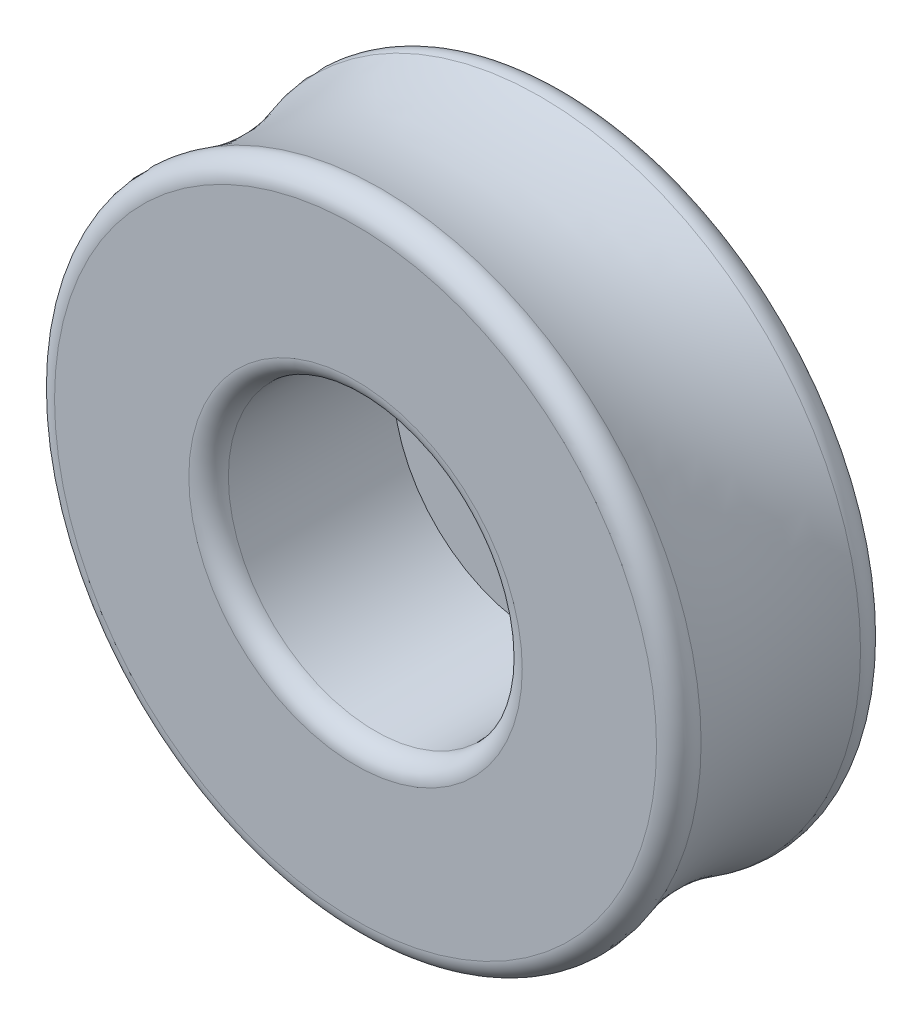
SolidWorks part; units mm, degrees
ref_plane "Front Plane" through (0, 0, 0) normal (0, 0, 1) x (1, 0, 0)
ref_plane "Top Plane" through (0, 0, 0) normal (0, 1, 0) x (1, 0, 0)
ref_plane "Right Plane" through (0, 0, 0) normal (1, 0, 0) x (0, 0, -1)
sketch "Sketch2" plane through (0, 0, 0) normal (0, 1, 0) x (1, 0, 0)
  line L1 (-12.5, -8) -> (12.5, -8)
  line L2 (-12.5, -8) -> (-12.5, 8)
  line L3 (-12.5, 8) -> (12.5, 8)
  line L4 (12.5, -8) -> (12.5, 8)
  line L5 (-12.5, -8) -> (12.5, 8) construction
  line L6 (-12.5, 8) -> (12.5, -8) construction
  line L7 (12.5, 8) -> (6.5, 8)
  line L8 (12.5, 8) -> (12.5, 15)
  line L9 (12.5, 15) -> (6.5, 15)
  line L10 (6.5, 8) -> (6.5, 15)
  line L11 (12.5, 15) -> (4.5, 15)
  line L12 (12.5, 15) -> (12.5, 17)
  line L13 (12.5, 17) -> (4.5, 17)
  line L14 (4.5, 15) -> (4.5, 17)
  arc A0 (-12.5, 8) -> (-12.5, -8) centre (-30.8303, 0) cw
  point P0 (0, 0)
  dimension "D1" = 7
  dimension "D2" = 16
  dimension "D3" = 25
  dimension "D4" = 6
  dimension "D5" = 8
  dimension "D6" = 2
revolve "Revolve1" add sketch "Sketch2" angle 360 about L4 region at (0.5563, 0, 0) region at (9.5, 0, -11.5) region at (8.5, 0, -16)
sketch "Sketch3" plane through (0, 0, 8) normal (0, 0, 1) x (1, 0, 0)
  circle A0 centre (12.5, 0) radius 11.15
  circle A1 centre (12.5, 0) radius 25 construction
  dimension "D1" = 22.3
extrude "Cut-Extrude1" cut sketch "Sketch3" against normal blind 14
sketch "Sketch8" plane through (0, 0, -6) normal (0, 0, 1) x (1, 0, 0)
  circle A0 centre (12.5, 0) radius 4.25
  circle A1 centre (12.5, 0) radius 11.15 construction
  dimension "D1" = 8.5
extrude "Cut-Extrude3" cut sketch "Sketch8" against normal through all
fillet "Fillet1" radius 1.5 1 edges at (16.75, 0, -6)
fillet "Fillet2" radius 1.5 3 edges at (37.5, 0, -8) (37.5, 0, 8) (23.65, 0, 8)
fillet "Fillet5" radius 1.5 1 edges at (16.75, 0, -17)
fillet "Fillet6" radius 1 2 edges at (20.5, 0, -15) (20.5, 0, -17)
